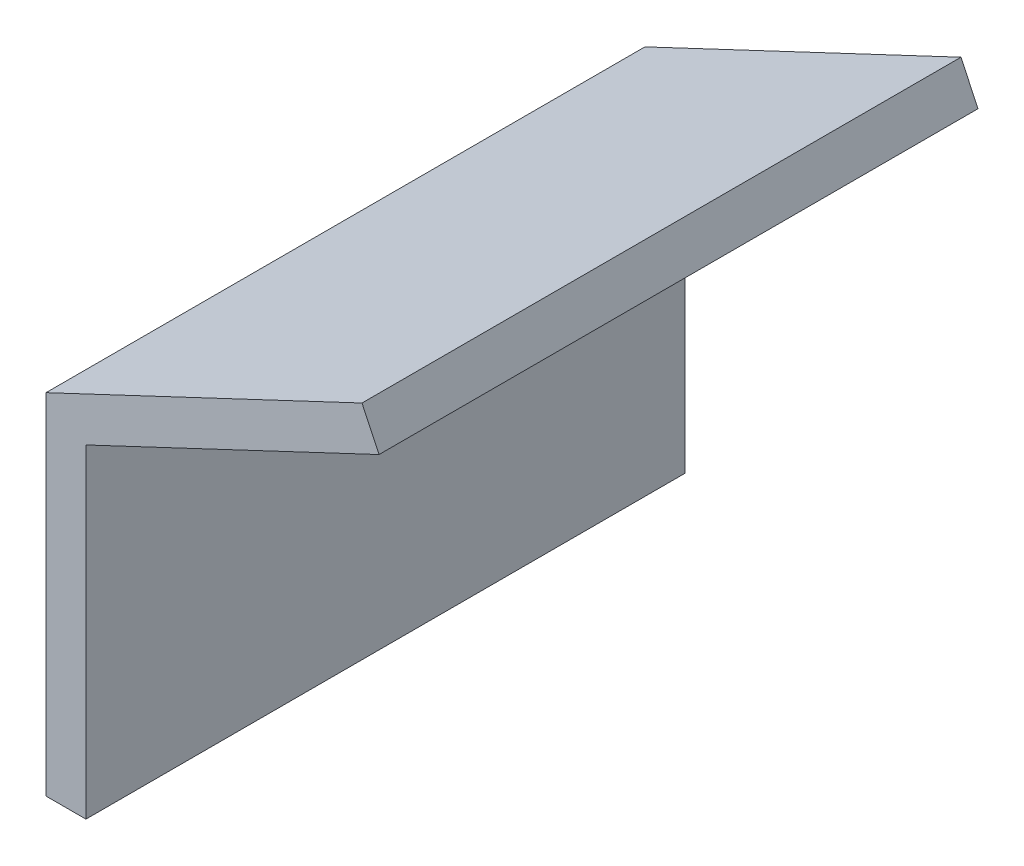
SolidWorks part; units mm, degrees
material "PLA"
ref_plane "Front Plane" through (0, 0, 0) normal (0, 0, 1) x (1, 0, 0)
ref_plane "Top Plane" through (0, 0, 0) normal (0, 1, 0) x (1, 0, 0)
ref_plane "Right Plane" through (0, 0, 0) normal (1, 0, 0) x (0, 0, -1)
sketch "Sketch1" plane through (0, 0, 0) normal (0, 0, 1) x (1, 0, 0)
  line L0 (0, 0) -> (63.3119, 29.8598)
  line L1 (0, 0) -> (0, -70)
  line L2 (8, -5.0721) -> (66.7244, 22.6242)
  line L3 (8, -5.0721) -> (8, -70)
  line L4 (63.3119, 29.8598) -> (66.7244, 22.6242)
  line L5 (0, -70) -> (8, -70)
  dimension "D1" = 70
  dimension "D2" = 70
  dimension "D3" = 115.25
  dimension "D4" = 8
extrude "Boss-Extrude1" add sketch "Sketch1" along normal mid plane 120
